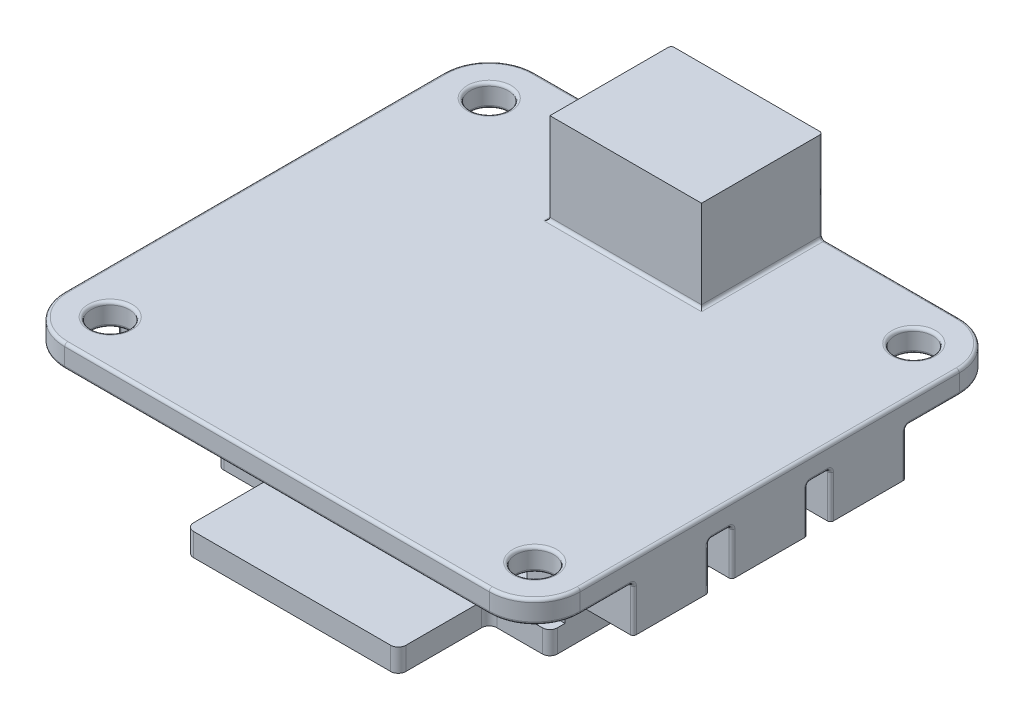
SolidWorks part; units mm, degrees
ref_plane "前视基准面" through (0, 0, 0) normal (0, 0, 1) x (1, 0, 0)
ref_plane "上视基准面" through (0, 0, 0) normal (0, 1, 0) x (1, 0, 0)
ref_plane "右视基准面" through (0, 0, 0) normal (1, 0, 0) x (0, 0, -1)
other "Configuration Table"
ref_axis "基准轴1" through (0, -46.8641, 0) along (0, 1, 0)
sketch "草图1" plane through (0, 0, 0) normal (0, 1, 0) x (1, 0, 0)
  line L3 (-17, 15.5) -> (17, 15.5)
  line L4 (-17, 15.5) -> (-17, -15.5)
  line L5 (-17, -15.5) -> (17, -15.5)
  line L6 (17, 15.5) -> (17, -15.5)
  line L7 (-17, 15.5) -> (17, -15.5) construction
  line L8 (-17, -15.5) -> (17, 15.5) construction
  point P0 (0, 0)
  dimension "D1" = 31
  dimension "D2" = 34
extrude "凸台-拉伸-PCB板" add sketch "草图1" along normal blind 1.5
sketch "草图2" plane through (0, 1.5, 0) normal (0, 1, 0) x (1, 0, 0)
  line L0 (17, -15.5) -> (17, 15.5) construction
  line L1 (14, 12.5) -> (-14, 12.5) construction
  line L2 (14, 12.5) -> (14, -12.5) construction
  line L3 (14, -12.5) -> (-14, -12.5) construction
  line L4 (-14, 12.5) -> (-14, -12.5) construction
  line L5 (-17, -15.5) -> (17, -15.5) construction
  line L6 (17, 15.5) -> (-17, 15.5) construction
  line L7 (-17, 15.5) -> (-17, -15.5) construction
  circle A0 centre (14, 12.5) radius 1.25
  circle A1 centre (-14, 12.5) radius 1.25
  circle A2 centre (-14, 12.5) radius 3
  circle A3 centre (14, 12.5) radius 3
  circle A4 centre (14, -12.5) radius 1.25
  circle A5 centre (14, -12.5) radius 3
  circle A6 centre (-14, -12.5) radius 1.25
  circle A7 centre (-14, -12.5) radius 3
  line M13 (17, -15.5) -> (17, 15.5)
  line M14 (17, 15.5) -> (-17, 15.5)
  line M15 (-17, 15.5) -> (-17, -15.5)
  line M16 (-17, -15.5) -> (17, -15.5)
  dimension "D1" = 2.5
  dimension "D2" = 6
extrude "切除-拉伸-PCB固定孔" cut sketch "草图2" against normal blind 1.5 contours A5 M16 M13 | A4 | A0 | A3 M13 M14 | A2 M14 M15 | A1 | A7 M15 M16 | A6 region at (14, 1.5, -12.5) region at (-14, 1.5, -12.5) region at (-16.3299, 1.5, -14.8299) region at (16.3299, 1.5, -14.8299) region at (-16.3299, 1.5, 14.8299) region at (16.3299, 1.5, 14.8299) region at (14, 1.5, 12.5) region at (-14, 1.5, 12.5)
sketch "草图4" plane through (0, 0, 0) normal (0, 1, 0) x (1, 0, 0)
  line L0 (0, 0) -> (0, -12.1937) construction
  line L1 (-17, 12.5) -> (-17, -12.5) construction
  line L2 (-17, 9) -> (-13, 9)
  line L3 (-17, 9) -> (-17, 4)
  line L4 (-17, 4) -> (-13, 4)
  line L5 (-13, 9) -> (-13, 4)
  line L7 (-17, 2.5) -> (-13, 2.5)
  line L8 (-17, 2.5) -> (-17, -2.5)
  line L9 (-17, -2.5) -> (-13, -2.5)
  line L10 (-13, 2.5) -> (-13, -2.5)
  line L19 (-17, 12.5) -> (-17, -12.5) construction
  line L20 (-17, -4) -> (-13, -4)
  line L21 (-17, -4) -> (-17, -9)
  line L22 (-17, -9) -> (-13, -9)
  line L23 (-13, -4) -> (-13, -9)
  line L24 (-13, 0) -> (0, 0) construction
  line L26 (-9.5, 11.5) -> (-5.5, 11.5)
  line L27 (-9.5, 11.5) -> (-9.5, 15.5)
  line L28 (-9.5, 15.5) -> (-5.5, 15.5)
  line L29 (-5.5, 11.5) -> (-5.5, 15.5)
  line L30 (17, 4) -> (13, 4)
  line L31 (-4.5, 11.5) -> (-0.5, 11.5)
  line L32 (-4.5, 11.5) -> (-4.5, 15.5)
  line L33 (-4.5, 15.5) -> (-0.5, 15.5)
  line L34 (-0.5, 11.5) -> (-0.5, 15.5)
  line L35 (0.5, 11.5) -> (4.5, 11.5)
  line L36 (0.5, 11.5) -> (0.5, 15.5)
  line L37 (0.5, 15.5) -> (4.5, 15.5)
  line L38 (4.5, 11.5) -> (4.5, 15.5)
  line L39 (5.5, 11.5) -> (9.5, 11.5)
  line L40 (5.5, 11.5) -> (5.5, 15.5)
  line L41 (5.5, 15.5) -> (9.5, 15.5)
  line L42 (9.5, 11.5) -> (9.5, 15.5)
  line L43 (13, 9) -> (13, 4)
  line L44 (17, 9) -> (13, 9)
  line L45 (17, 9) -> (17, 4)
  line L46 (17, -2.5) -> (13, -2.5)
  line L47 (13, 2.5) -> (13, -2.5)
  line L48 (17, 2.5) -> (13, 2.5)
  line L49 (17, 2.5) -> (17, -2.5)
  line L50 (17, -9) -> (13, -9)
  line L51 (13, -4) -> (13, -9)
  line L52 (17, -4) -> (13, -4)
  line L53 (17, -4) -> (17, -9)
  line L54 (14, 15.5) -> (-14, 15.5) construction
  dimension "D1" = 5
  dimension "D2" = 4
  dimension "D3" = 1
  dimension "D4" = 18
  dimension "D5" = 4
  dimension "D6" = 1
  dimension "D7" = 1
  dimension "D8" = 4
extrude "凸台-拉伸1" add sketch "草图4" against normal blind 3
sketch "草图3" plane through (0, 1.5, 0) normal (0, 1, 0) x (1, 0, 0)
  line L1 (-5, 15.5) -> (5, 15.5)
  line L2 (-5, 15.5) -> (-5, 7.5)
  line L3 (-5, 7.5) -> (5, 7.5)
  line L4 (5, 15.5) -> (5, 7.5)
  line L5 (0, 0) -> (0, 15.5) construction
  line L6 (14, 15.5) -> (-14, 15.5) construction
  dimension "D1" = 10
  dimension "D2" = 8
extrude "凸台-拉伸-电源口" add sketch "草图3" along normal blind 6
sketch "草图7" plane through (0, 0, 0) normal (0, -1, 0) x (1, 0, 0)
  line L0 (0, 0) -> (0, 8.4067) construction
  line L1 (11, 7.5) -> (8.5, 7.5)
  line L2 (11, 7.5) -> (11, -8.5)
  line L3 (11, -8.5) -> (8.5, -8.5)
  line L4 (8.5, 7.5) -> (8.5, -8.5)
  line L5 (17, 12.5) -> (17, 9) construction
  line L6 (-14, 15.5) -> (14, 15.5) construction
  line L7 (-11, -8.5) -> (-8.5, -8.5)
  line L8 (-8.5, 7.5) -> (-8.5, -8.5)
  line L9 (-11, 7.5) -> (-8.5, 7.5)
  line L10 (-11, 7.5) -> (-11, -8.5)
  dimension "D1" = 16
  dimension "D2" = 2.5
  dimension "D3" = 6
  dimension "D4" = 8
extrude "凸台-拉伸-插排" add sketch "草图7" along normal blind 6
sketch "草图8" plane through (0, -6, 0) normal (0, -1, 0) x (1, 0, 0)
  line L0 (-11, 8.5) -> (-7, 8.5)
  line L1 (-7, 8.5) -> (-7, 14.5)
  line L2 (-7, 14.5) -> (7, 14.5)
  line L3 (7, 14.5) -> (7, 8.5)
  line L4 (7, 8.5) -> (11, 8.5)
  line L5 (11, 8.5) -> (11, -8.5)
  line L6 (11, -8.5) -> (5.5, -8.5)
  line L7 (5.5, -8.5) -> (5.5, -12.5)
  line L8 (5.5, -12.5) -> (-5.5, -12.5)
  line L9 (-5.5, -12.5) -> (-5.5, -8.5)
  line L10 (-5.5, -8.5) -> (-11, -8.5)
  line L11 (-11, -8.5) -> (-11, 8.5)
  line L12 (0, -12.5) -> (0, 14.5) construction
  line L13 (14, -15.5) -> (9.5, -15.5) construction
  point P19 (0, -12.5)
  dimension "D1" = 14
  dimension "D2" = 11
  dimension "D3" = 17
  dimension "D4" = 22
  dimension "D5" = 4
  dimension "D6" = 6
  dimension "D7" = 3
extrude "凸台-拉伸-C3核心板" add sketch "草图8" along normal blind 1.5
ref_plane "基准面1" through (0, 0, -6.5) normal (0, 0, -1) x (-1, 0, 0)
sketch "草图9" plane through (0, 0, -6.5) normal (0, 0, -1) x (-1, 0, 0)
  line L0 (-3, -9) -> (3, -9) construction
  line L1 (-3, -7.5) -> (3, -7.5)
  line L2 (-3, -10.5) -> (3, -10.5)
  line L3 (0, -46.8641) -> (0, 170.1769) construction
  line L4 (5.5, -7.5) -> (-5.5, -7.5) construction
  arc A0 (-3, -7.5) -> (-3, -10.5) centre (-3, -9) ccw
  arc A1 (3, -10.5) -> (3, -7.5) centre (3, -9) ccw
  point P2 (0, -9)
  point P7 (-4.5, -9)
  point P8 (4.5, -9)
  dimension "D1" = 9
  dimension "D2" = 3
extrude "凸台-拉伸-USB-C" add sketch "草图9" along normal blind 7
fillet "圆角1" radius 0.5 12 edges at (-11, -6.75, 8.5) (-7, -6.75, 14.5) (-7, -6.75, 8.5) (7, -6.75, 8.5) (7, -6.75, 14.5) (11, -6.75, 8.5) (11, -3.75, -8.5) (5.5, -6.75, -8.5) (-5.5, -6.75, -8.5) (-11, -3.75, -8.5) (-5.5, -6.75, -12.5) (5.5, -6.75, -12.5)
sketch "草图10" plane through (0, -7.5, 0) normal (0, -1, 0) x (1, 0, 0)
  line L0 (-17, -12.5) -> (-17, -9) construction
  line L1 (-4.8, -2.3) -> (-2.8, -2.3)
  line L2 (-4.8, -2.3) -> (-4.8, -4.3)
  line L3 (-4.8, -4.3) -> (-2.8, -4.3)
  line L4 (-2.8, -2.3) -> (-2.8, -4.3)
  line L5 (-9.5, -15.5) -> (-14, -15.5) construction
  dimension "D1" = 12.2
  dimension "D2" = 11.2
  dimension "D3" = 2
extrude "凸台-拉伸-LED" add sketch "草图10" along normal blind 1
fillet "圆角2" radius 0.2 100 edges at (17, -1.5, 4) (17, -1.5, 2.5) (17, -1.5, -2.5) (17, -1.5, -4) (17, -1.5, -9) (9.5, -1.5, -15.5) (5.5, -1.5, -15.5) (4.5, -1.5, -15.5) (0.5, -1.5, -15.5) (-0.5, -1.5, -15.5) (-4.5, -1.5, -15.5) (-5.5, -1.5, -15.5) (-9.5, -1.5, -15.5) (-17, -1.5, -9) (-17, -1.5, -4) (-17, -1.5, -2.5) (-17, -1.5, 2.5) (-17, -1.5, 4) (-17, -1.5, 9) (17, -1.5, 9) (5, 4.5, -15.5) (-5, 4.5, -15.5) (-10.8536, 0, -8.3536) (-9.5, 0, -8.5) (-8.5, 0, -0.5) (-9.75, 0, 7.5) (-11, 0, -0.25) (-14, 0, -11.25) (-14, 0, 13.75) (14, 0, 13.75) (14, 0, -11.25) (15, 0, 4) (17, 0, 3.25) (15, 0, 2.5) (13, 0, 0) (15, 0, -2.5) (17, 0, -3.25) (15, 0, -4) (13, 0, -6.5) (15, 0, -9) (17, 0, -10.75) (16.1213, 0, -14.6213) (11.75, 0, -15.5) (9.5, 0, -13.5) (7.5, 0, -11.5) (5.5, 0, -13.5) (5, 0, -15.5) (4.5, 0, -13.5) (2.5, 0, -11.5) (0.5, 0, -13.5) (0, 0, -15.5) (-0.5, 0, -13.5) (-2.5, 0, -11.5) (-4.5, 0, -13.5) (-5, 0, -15.5) (-5.5, 0, -13.5) (-7.5, 0, -11.5) (-9.5, 0, -13.5) (-11.75, 0, -15.5) (-16.1213, 0, -14.6213) (-17, 0, -10.75) (-15, 0, -9) (-13, 0, -6.5) (-15, 0, -4) (-17, 0, -3.25) (-15, 0, -2.5) (-13, 0, 0) (-15, 0, 2.5) (-17, 0, 3.25) (-15, 0, 4) (-13, 0, 6.5) (-15, 0, 9) (-17, 0, 10.75) (-16.1213, 0, 14.6213) (0, 0, 15.5) (16.1213, 0, 14.6213) (17, 0, 10.75) (15, 0, 9) (13, 0, 6.5) (9.75, 0, 7.5) (8.5, 0, -0.5) (9.5, 0, -8.5) (10.8536, 0, -8.3536) (11, 0, -0.25) (-14, 1.5, -11.25) (-14, 1.5, 13.75) (14, 1.5, 13.75) (14, 1.5, -11.25) (0, 1.5, -7.5) (5, 1.5, -11.5) (9.5, 1.5, -15.5) (16.1213, 1.5, -14.6213) (17, 1.5, 0) (16.1213, 1.5, 14.6213) (0, 1.5, 15.5) (-16.1213, 1.5, 14.6213) (-17, 1.5, 0) (-16.1213, 1.5, -14.6213) (-9.5, 1.5, -15.5) (-5, 1.5, -11.5)
